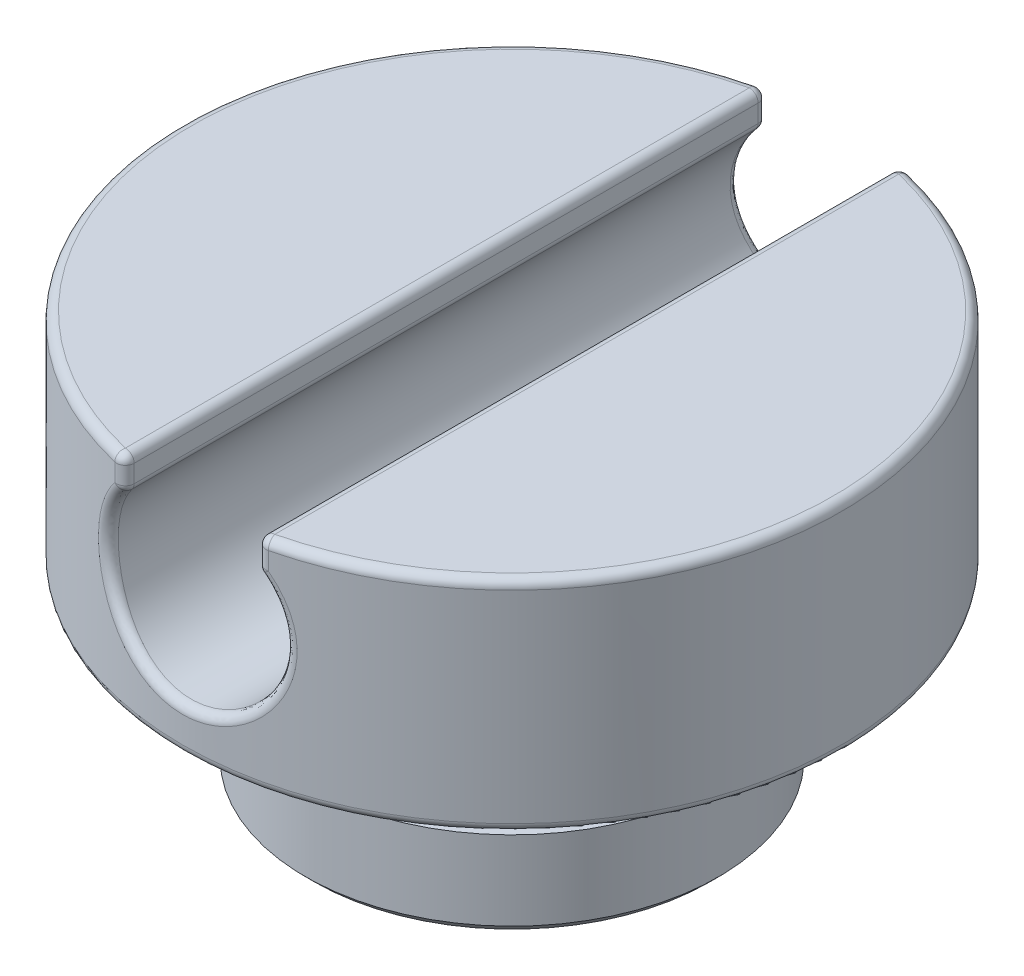
SolidWorks part; units mm, degrees
ref_plane "前视基准面" through (0, 0, 0) normal (0, 0, 1) x (1, 0, 0)
ref_plane "上视基准面" through (0, 0, 0) normal (0, 1, 0) x (1, 0, 0)
ref_plane "右视基准面" through (0, 0, 0) normal (1, 0, 0) x (0, 0, -1)
sketch "草图1" plane through (0, 0, 0) normal (0, 1, 0) x (1, 0, 0)
  circle A0 centre (0, 0) radius 7.5
  dimension "D1" = 15
extrude "凸台-拉伸1" add sketch "草图1" against normal blind 5
sketch "草图2" plane through (0, -5, 0) normal (0, -1, 0) x (1, 0, 0)
  circle A0 centre (0, 0) radius 4.3
  dimension "D1" = 8.6
extrude "凸台-拉伸2" add sketch "草图2" along normal blind 2
sketch "草图3" plane through (0, -7, 0) normal (0, -1, 0) x (1, 0, 0)
  circle A0 centre (0, 0) radius 4.7
  dimension "D1" = 9.4
extrude "凸台-拉伸3" add sketch "草图3" along normal blind 2
sketch "草图4" plane through (0, 0, 0) normal (0, 0, 1) x (1, 0, 0)
  line L0 (0, 0) -> (0, -2) construction
  line L1 (0, 0) -> (-1.5, 0)
  line L2 (7.5, 0) -> (-7.5, 0) construction
  line L3 (-1.5, 0) -> (-1.5, -0.6771)
  line L4 (0, 0) -> (1.5, 0)
  line L5 (1.5, 0) -> (1.5, -0.6771)
  arc A0 (-1.5, -0.6771) -> (1.5, -0.6771) centre (0, -2) ccw
  dimension "D1" = 2
  dimension "D2" = 1.5
  dimension "D3" = 1.5
extrude "切除-拉伸1" cut sketch "草图4" against normal up to next and the other way up to next
sketch "草图5" plane through (0, -9, 0) normal (0, -1, 0) x (1, 0, 0)
  circle A0 centre (0, 0) radius 3.2
  dimension "D1" = 6.4
extrude "切除-拉伸2" cut sketch "草图5" against normal blind 4
fillet "圆角1" radius 0.2 14 edges at (1.5, 0, 0) (7.5, 0, 0) (-1.5, 0, 0) (-7.5, 0, 0) (0, -5, 4.3) (0, -5, 7.5) (-1.5, -0.6771, 0) (1.5, -0.6771, 0) (1.5, -0.3386, -7.3485) (0.0844, -3.9982, -7.4995) (-1.5, -0.3386, -7.3485) (1.5, -0.3386, 7.3485) (0.0844, -3.9982, 7.4995) (-1.5, -0.3386, 7.3485)
chamfer "倒角1" distance 0.2 angle 45 1 edges at (0, -9, -4.7)
